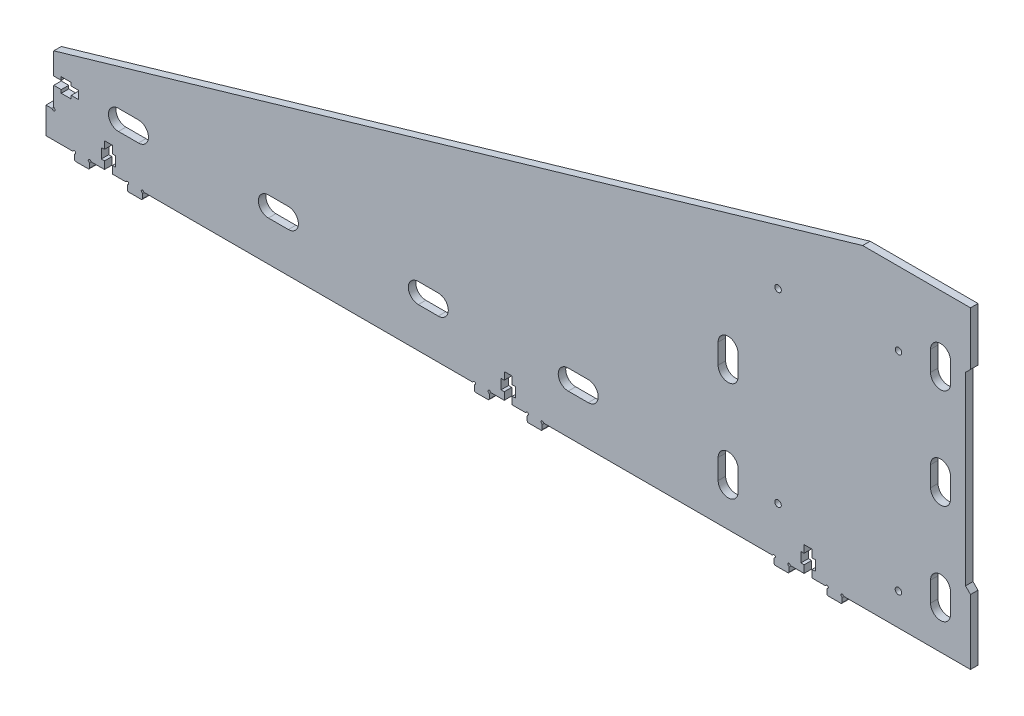
SolidWorks part; units mm, degrees
ref_plane "Alzado" through (0, 0, 0) normal (0, 0, 1) x (1, 0, 0)
ref_plane "Planta" through (0, 0, 0) normal (0, 1, 0) x (1, 0, 0)
ref_plane "Vista lateral" through (0, 0, 0) normal (1, 0, 0) x (0, 0, -1)
sketch "Model" plane through (0, 0, 0) normal (0, 0, 1) x (1, 0, 0)
  line L0 (448.0081, 367.9963) -> (446.0081, 365.9963)
  line L1 (446.0081, 365.9963) -> (446.0081, 291.9963)
  line L2 (446.0081, 263.9963) -> (437.4741, 263.9963)
  line L3 (408.5421, 263.9963) -> (397.4741, 263.9963)
  line L4 (396.6081, 263.1303) -> (396.6081, 261.4963)
  line L5 (396.1081, 260.9963) -> (391.1081, 260.9963)
  line L6 (390.6081, 261.4963) -> (390.6081, 263.1303)
  line L7 (389.7421, 263.9963) -> (384.6081, 263.9963)
  line L8 (384.6081, 263.9963) -> (384.6081, 266.9963)
  line L9 (384.6081, 266.9963) -> (385.8831, 266.9963)
  line L10 (385.8831, 266.9963) -> (385.8831, 270.9963)
  line L11 (385.8831, 270.9963) -> (384.6081, 270.9963)
  line L12 (384.6081, 270.9963) -> (384.6081, 273.9963)
  line L13 (384.6081, 273.9963) -> (381.4081, 273.9963)
  line L14 (381.4081, 273.9963) -> (381.4081, 270.9963)
  line L15 (381.4081, 270.9963) -> (380.1331, 270.9963)
  line L16 (380.1331, 270.9963) -> (380.1331, 266.9963)
  line L17 (380.1331, 266.9963) -> (381.4081, 266.9963)
  line L18 (381.4081, 266.9963) -> (381.4081, 263.9963)
  line L19 (381.4081, 263.9963) -> (376.2741, 263.9963)
  line L20 (375.4081, 263.1303) -> (375.4081, 261.4963)
  line L21 (374.9081, 260.9963) -> (369.9081, 260.9963)
  line L22 (369.4081, 261.4963) -> (369.4081, 263.1303)
  line L23 (368.5421, 263.9963) -> (277.4741, 263.9963)
  line L24 (276.6081, 263.1303) -> (276.6081, 261.4963)
  line L25 (276.1081, 260.9963) -> (271.1081, 260.9963)
  line L26 (270.6081, 261.4963) -> (270.6081, 263.1303)
  line L27 (269.7421, 263.9963) -> (264.6081, 263.9963)
  line L28 (264.6081, 263.9963) -> (264.6081, 266.9963)
  line L29 (264.6081, 266.9963) -> (265.8831, 266.9963)
  line L30 (265.8831, 266.9963) -> (265.8831, 270.9963)
  line L31 (265.8831, 270.9963) -> (264.6081, 270.9963)
  line L32 (264.6081, 270.9963) -> (264.6081, 273.9963)
  line L33 (264.6081, 273.9963) -> (261.4081, 273.9963)
  line L34 (261.4081, 273.9963) -> (261.4081, 270.9963)
  line L35 (261.4081, 270.9963) -> (260.1331, 270.9963)
  line L36 (260.1331, 270.9963) -> (260.1331, 266.9963)
  line L37 (260.1331, 266.9963) -> (261.4081, 266.9963)
  line L38 (261.4081, 266.9963) -> (261.4081, 263.9963)
  line L39 (261.4081, 263.9963) -> (256.2741, 263.9963)
  line L40 (255.4081, 263.1303) -> (255.4081, 261.4963)
  line L41 (254.9081, 260.9963) -> (249.9081, 260.9963)
  line L42 (249.4081, 261.4963) -> (249.4081, 263.1303)
  line L43 (248.5421, 263.9963) -> (117.4741, 263.9963)
  line L44 (116.6081, 263.1303) -> (116.6081, 261.4963)
  line L45 (116.1081, 260.9963) -> (111.1081, 260.9963)
  line L46 (110.6081, 261.4963) -> (110.6081, 263.1303)
  line L47 (109.7421, 263.9963) -> (104.6081, 263.9963)
  line L48 (104.6081, 263.9963) -> (104.6081, 266.9963)
  line L49 (104.6081, 266.9963) -> (105.8831, 266.9963)
  line L50 (105.8831, 266.9963) -> (105.8831, 270.9963)
  line L51 (105.8831, 270.9963) -> (104.6081, 270.9963)
  line L52 (104.6081, 270.9963) -> (104.6081, 273.9963)
  line L53 (104.6081, 273.9963) -> (101.4081, 273.9963)
  line L54 (101.4081, 273.9963) -> (101.4081, 270.9963)
  line L55 (101.4081, 270.9963) -> (100.1331, 270.9963)
  line L56 (100.1331, 270.9963) -> (100.1331, 266.9963)
  line L57 (100.1331, 266.9963) -> (101.4081, 266.9963)
  line L58 (101.4081, 266.9963) -> (101.4081, 263.9963)
  line L59 (101.4081, 263.9963) -> (96.2741, 263.9963)
  line L60 (95.4081, 263.1303) -> (95.4081, 261.4963)
  line L61 (94.9081, 260.9963) -> (89.9081, 260.9963)
  line L62 (89.4081, 261.4963) -> (89.4081, 263.1303)
  line L63 (88.5421, 263.9963) -> (78.0081, 263.9963)
  line L64 (78.0081, 263.9963) -> (78.0081, 274.6463)
  line L65 (78.0081, 274.6463) -> (80.2421, 274.6463)
  line L66 (81.1081, 275.5123) -> (81.1081, 283.0463)
  line L67 (81.1081, 283.0463) -> (84.1081, 283.0463)
  line L68 (84.1081, 283.0463) -> (84.1081, 281.7713)
  line L69 (84.1081, 281.7713) -> (88.1081, 281.7713)
  line L70 (88.1081, 281.7713) -> (88.1081, 283.0463)
  line L71 (88.1081, 283.0463) -> (91.1081, 283.0463)
  line L72 (91.1081, 283.0463) -> (91.1081, 286.2463)
  line L73 (91.1081, 286.2463) -> (88.1081, 286.2463)
  line L74 (88.1081, 286.2463) -> (88.1081, 287.5213)
  line L75 (88.1081, 287.5213) -> (84.1081, 287.5213)
  line L76 (84.1081, 287.5213) -> (84.1081, 286.2463)
  line L77 (84.1081, 286.2463) -> (81.1081, 286.2463)
  line L78 (81.1081, 286.2463) -> (81.1081, 294.9945)
  line L79 (81.1081, 294.9945) -> (403.1976, 388.8913)
  line L80 (115.0081, 287.9963) -> (107.0081, 287.9963)
  line L81 (107.0081, 279.9963) -> (115.0081, 279.9963)
  line L82 (175.0081, 287.9963) -> (167.0081, 287.9963)
  line L83 (167.0081, 279.9963) -> (175.0081, 279.9963)
  line L84 (235.0081, 287.9963) -> (227.0081, 287.9963)
  line L85 (227.0081, 279.9963) -> (235.0081, 279.9963)
  line L86 (295.0081, 287.9963) -> (287.0081, 287.9963)
  line L87 (287.0081, 279.9963) -> (295.0081, 279.9963)
  line L88 (355.0081, 278.9963) -> (355.0081, 286.9963)
  line L89 (347.0081, 286.9963) -> (347.0081, 278.9963)
  line L90 (355.0081, 318.9963) -> (355.0081, 326.9963)
  line L91 (347.0081, 326.9963) -> (347.0081, 318.9963)
  line L92 (440.0081, 278.9963) -> (440.0081, 286.9963)
  line L93 (432.0081, 286.9963) -> (432.0081, 278.9963)
  line L94 (440.0081, 318.9963) -> (440.0081, 326.9963)
  line L95 (432.0081, 326.9963) -> (432.0081, 318.9963)
  line L96 (440.0081, 358.9963) -> (440.0081, 366.9963)
  line L97 (432.0081, 366.9963) -> (432.0081, 358.9963)
  line L98 (448.0081, 389.3713) -> (448.0081, 367.9963)
  line L99 (408.5421, 263.9963) -> (437.4741, 263.9963)
  line L100 (446.0081, 263.9963) -> (448.0081, 263.9963)
  line L101 (448.0081, 263.9963) -> (448.0081, 289.9963)
  line L102 (448.0081, 289.9963) -> (446.0081, 291.9963)
  line L103 (404.8442, 389.3713) -> (448.0081, 389.3713)
  line L104 (403.1976, 388.8913) -> (404.8442, 389.3713)
  arc A0 (397.0411, 264.2463) -> (397.4741, 263.9963) centre (397.4741, 264.4963) ccw
  arc A1 (397.0411, 264.2463) -> (396.3581, 263.5633) centre (396.6081, 263.9963) ccw
  arc A2 (396.6081, 263.1303) -> (396.3581, 263.5633) centre (396.1081, 263.1303) ccw
  arc A3 (396.1081, 260.9963) -> (396.6081, 261.4963) centre (396.1081, 261.4963) ccw
  arc A4 (390.6081, 261.4963) -> (391.1081, 260.9963) centre (391.1081, 261.4963) ccw
  arc A5 (390.8581, 263.5633) -> (390.6081, 263.1303) centre (391.1081, 263.1303) ccw
  arc A6 (390.8581, 263.5633) -> (390.1751, 264.2463) centre (390.6081, 263.9963) ccw
  arc A7 (389.7421, 263.9963) -> (390.1751, 264.2463) centre (389.7421, 264.4963) ccw
  arc A8 (375.8411, 264.2463) -> (376.2741, 263.9963) centre (376.2741, 264.4963) ccw
  arc A9 (375.8411, 264.2463) -> (375.1581, 263.5633) centre (375.4081, 263.9963) ccw
  arc A10 (375.4081, 263.1303) -> (375.1581, 263.5633) centre (374.9081, 263.1303) ccw
  arc A11 (374.9081, 260.9963) -> (375.4081, 261.4963) centre (374.9081, 261.4963) ccw
  arc A12 (369.4081, 261.4963) -> (369.9081, 260.9963) centre (369.9081, 261.4963) ccw
  arc A13 (369.6581, 263.5633) -> (369.4081, 263.1303) centre (369.9081, 263.1303) ccw
  arc A14 (369.6581, 263.5633) -> (368.9751, 264.2463) centre (369.4081, 263.9963) ccw
  arc A15 (368.5421, 263.9963) -> (368.9751, 264.2463) centre (368.5421, 264.4963) ccw
  arc A16 (277.0411, 264.2463) -> (277.4741, 263.9963) centre (277.4741, 264.4963) ccw
  arc A17 (277.0411, 264.2463) -> (276.3581, 263.5633) centre (276.6081, 263.9963) ccw
  arc A18 (276.6081, 263.1303) -> (276.3581, 263.5633) centre (276.1081, 263.1303) ccw
  arc A19 (276.1081, 260.9963) -> (276.6081, 261.4963) centre (276.1081, 261.4963) ccw
  arc A20 (270.6081, 261.4963) -> (271.1081, 260.9963) centre (271.1081, 261.4963) ccw
  arc A21 (270.8581, 263.5633) -> (270.6081, 263.1303) centre (271.1081, 263.1303) ccw
  arc A22 (270.8581, 263.5633) -> (270.1751, 264.2463) centre (270.6081, 263.9963) ccw
  arc A23 (269.7421, 263.9963) -> (270.1751, 264.2463) centre (269.7421, 264.4963) ccw
  arc A24 (255.8411, 264.2463) -> (256.2741, 263.9963) centre (256.2741, 264.4963) ccw
  arc A25 (255.8411, 264.2463) -> (255.1581, 263.5633) centre (255.4081, 263.9963) ccw
  arc A26 (255.4081, 263.1303) -> (255.1581, 263.5633) centre (254.9081, 263.1303) ccw
  arc A27 (254.9081, 260.9963) -> (255.4081, 261.4963) centre (254.9081, 261.4963) ccw
  arc A28 (249.4081, 261.4963) -> (249.9081, 260.9963) centre (249.9081, 261.4963) ccw
  arc A29 (249.6581, 263.5633) -> (249.4081, 263.1303) centre (249.9081, 263.1303) ccw
  arc A30 (249.6581, 263.5633) -> (248.9751, 264.2463) centre (249.4081, 263.9963) ccw
  arc A31 (248.5421, 263.9963) -> (248.9751, 264.2463) centre (248.5421, 264.4963) ccw
  arc A32 (117.0411, 264.2463) -> (117.4741, 263.9963) centre (117.4741, 264.4963) ccw
  arc A33 (117.0411, 264.2463) -> (116.3581, 263.5633) centre (116.6081, 263.9963) ccw
  arc A34 (116.6081, 263.1303) -> (116.3581, 263.5633) centre (116.1081, 263.1303) ccw
  arc A35 (116.1081, 260.9963) -> (116.6081, 261.4963) centre (116.1081, 261.4963) ccw
  arc A36 (110.6081, 261.4963) -> (111.1081, 260.9963) centre (111.1081, 261.4963) ccw
  arc A37 (110.8581, 263.5633) -> (110.6081, 263.1303) centre (111.1081, 263.1303) ccw
  arc A38 (110.8581, 263.5633) -> (110.1751, 264.2463) centre (110.6081, 263.9963) ccw
  arc A39 (109.7421, 263.9963) -> (110.1751, 264.2463) centre (109.7421, 264.4963) ccw
  arc A40 (95.8411, 264.2463) -> (96.2741, 263.9963) centre (96.2741, 264.4963) ccw
  arc A41 (95.8411, 264.2463) -> (95.1581, 263.5633) centre (95.4081, 263.9963) ccw
  arc A42 (95.4081, 263.1303) -> (95.1581, 263.5633) centre (94.9081, 263.1303) ccw
  arc A43 (94.9081, 260.9963) -> (95.4081, 261.4963) centre (94.9081, 261.4963) ccw
  arc A44 (89.4081, 261.4963) -> (89.9081, 260.9963) centre (89.9081, 261.4963) ccw
  arc A45 (89.6581, 263.5633) -> (89.4081, 263.1303) centre (89.9081, 263.1303) ccw
  arc A46 (89.6581, 263.5633) -> (88.9751, 264.2463) centre (89.4081, 263.9963) ccw
  arc A47 (88.5421, 263.9963) -> (88.9751, 264.2463) centre (88.5421, 264.4963) ccw
  arc A48 (80.6751, 274.3963) -> (80.2421, 274.6463) centre (80.2421, 274.1463) ccw
  arc A49 (80.6751, 274.3963) -> (81.3581, 275.0793) centre (81.1081, 274.6463) ccw
  arc A50 (81.1081, 275.5123) -> (81.3581, 275.0793) centre (81.6081, 275.5123) ccw
  arc A51 (107.0081, 287.9963) -> (107.0081, 279.9963) centre (107.0081, 283.9963) ccw
  arc A52 (115.0081, 279.9963) -> (115.0081, 287.9963) centre (115.0081, 283.9963) ccw
  arc A53 (167.0081, 287.9963) -> (167.0081, 279.9963) centre (167.0081, 283.9963) ccw
  arc A54 (175.0081, 279.9963) -> (175.0081, 287.9963) centre (175.0081, 283.9963) ccw
  arc A55 (227.0081, 287.9963) -> (227.0081, 279.9963) centre (227.0081, 283.9963) ccw
  arc A56 (235.0081, 279.9963) -> (235.0081, 287.9963) centre (235.0081, 283.9963) ccw
  arc A57 (287.0081, 287.9963) -> (287.0081, 279.9963) centre (287.0081, 283.9963) ccw
  arc A58 (295.0081, 279.9963) -> (295.0081, 287.9963) centre (295.0081, 283.9963) ccw
  arc A59 (355.0081, 286.9963) -> (347.0081, 286.9963) centre (351.0081, 286.9963) ccw
  arc A60 (347.0081, 278.9963) -> (355.0081, 278.9963) centre (351.0081, 278.9963) ccw
  arc A61 (355.0081, 326.9963) -> (347.0081, 326.9963) centre (351.0081, 326.9963) ccw
  arc A62 (347.0081, 318.9963) -> (355.0081, 318.9963) centre (351.0081, 318.9963) ccw
  arc A63 (440.0081, 286.9963) -> (432.0081, 286.9963) centre (436.0081, 286.9963) ccw
  arc A64 (432.0081, 278.9963) -> (440.0081, 278.9963) centre (436.0081, 278.9963) ccw
  arc A65 (440.0081, 326.9963) -> (432.0081, 326.9963) centre (436.0081, 326.9963) ccw
  arc A66 (432.0081, 318.9963) -> (440.0081, 318.9963) centre (436.0081, 318.9963) ccw
  arc A67 (440.0081, 366.9963) -> (432.0081, 366.9963) centre (436.0081, 366.9963) ccw
  arc A68 (432.0081, 358.9963) -> (440.0081, 358.9963) centre (436.0081, 358.9963) ccw
  circle A69 centre (419.1695, 276.7848) radius 1.3
  circle A70 centre (419.1904, 359.9848) radius 1.3
  circle A71 centre (370.9755, 283.0078) radius 1.3
  circle A72 centre (370.9922, 357.5078) radius 1.3
extrude "Saliente-Extruir1" add sketch "Model" along normal blind 3
